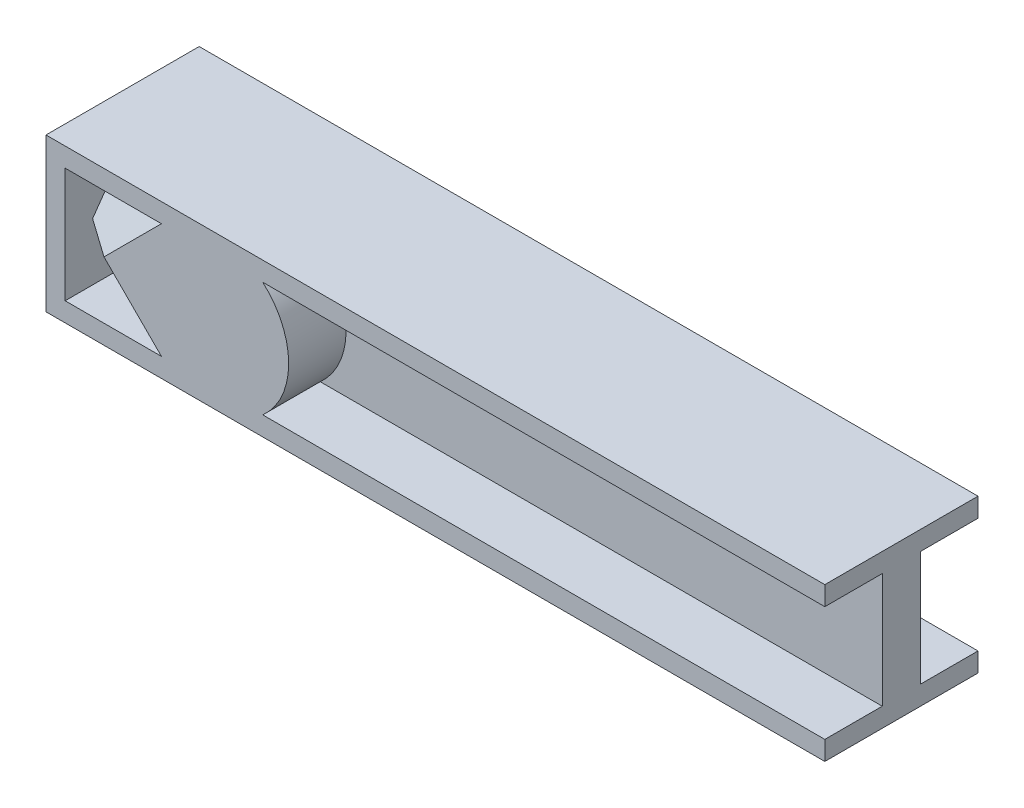
SolidWorks part; units mm, degrees
ref_plane "Front Plane" through (0, 0, 0) normal (0, 0, 1) x (1, 0, 0)
ref_plane "Top Plane" through (0, 0, 0) normal (0, 1, 0) x (1, 0, 0)
ref_plane "Right Plane" through (0, 0, 0) normal (1, 0, 0) x (0, 0, -1)
sketch "Sketch1" plane through (0, 0, 0) normal (0, 1, 0) x (1, 0, 0)
  line L0 (-40, -10) -> (-40, 10)
  line L1 (-40, -10) -> (40, -10)
  line L2 (-40, 10) -> (40, 10)
  line L3 (40, -10) -> (40, 10)
  line L4 (-40, -10) -> (40, 10) construction
  line L5 (-40, 10) -> (40, -10) construction
  point P1 (0, 0)
  dimension "D1" = 80
  dimension "D2" = 20
extrude "Boss-Extrude1" add sketch "Sketch1" along normal mid plane 20
sketch "Sketch2" plane through (0, 0, 0) normal (0, 1, 0) x (1, 0, 0)
  line L0 (40, 10) -> (40, 2.5)
  line L1 (40, -10) -> (-40, -10)
  line L2 (-40, -10) -> (-40, -2.5)
  line L3 (-40, 10) -> (40, 10)
  line L4 (-40, 2.5) -> (40, 2.5)
  line L6 (40, -2.5) -> (-40, -2.5)
  line L8 (0, 2.5) -> (0, -2.5) construction
  line L9 (-40, 2.5) -> (-40, 10)
  line L10 (40, -2.5) -> (40, -10)
  point P14 (0, 0)
  dimension "D1" = 5
extrude "Cut-Extrude1" cut sketch "Sketch2" against normal mid plane 15
sketch "Sketch3" plane through (0, 0, 0) normal (0, 0, 1) x (1, 0, 0)
  line L0 (-46.6144, 7.5) -> (-54.1144, 0)
  line L1 (-59.185, 7.5) -> (-46.6144, 7.5)
  line L6 (-40, -7.5) -> (-40, 7.5) construction
  line L7 (-59.185, 7.5) -> (-59.185, -7.5)
  line L13 (-40, 10) -> (-61.685, 10)
  line L15 (-40, -10) -> (-61.685, -10)
  line L16 (-61.685, 10) -> (-61.685, -10)
  line L17 (-59.185, -7.5) -> (-46.6144, -7.5)
  line L19 (-54.1144, 0) -> (-46.6144, -7.5)
  arc A4 (-40, -10) -> (-40, 10) centre (-40, 0) ccw
  point P12 (-59.185, 0)
  dimension "D1" = 2.5
  dimension "D2" = 2.5
extrude "Boss-Extrude2" add sketch "Sketch3" along normal mid plane 20
sketch "Sketch4" plane through (0, 0, 0) normal (0, 0, 1) x (1, 0, 0)
  line L6 (-59.185, 7.5) -> (-33.3856, 7.5)
  line L8 (-59.185, 7.5) -> (-59.185, -7.5)
  line L9 (-59.185, -7.5) -> (-33.3856, -7.5)
  line L10 (-33.3856, 7.5) -> (-33.3856, -7.5)
extrude "Boss-Extrude3" add sketch "Sketch4" along normal mid plane 5
ref_plane "Plane1" through (-71.685, 0, 0) normal (-1, 0, 0) x (0, 0, 1)
sketch "Sketch6" plane through (-71.685, 0, 0) normal (-1, 0, 0) x (0, 0, 1)
  circle A0 centre (0, 0) radius 7.9009
chamfer "Chamfer1" distance 7.5 angle 45 4 edges at (-50.3644, -3.75, -2.5) (-50.3644, 3.75, -2.5) (-50.3644, -3.75, 2.5) (-50.3644, 3.75, 2.5)
